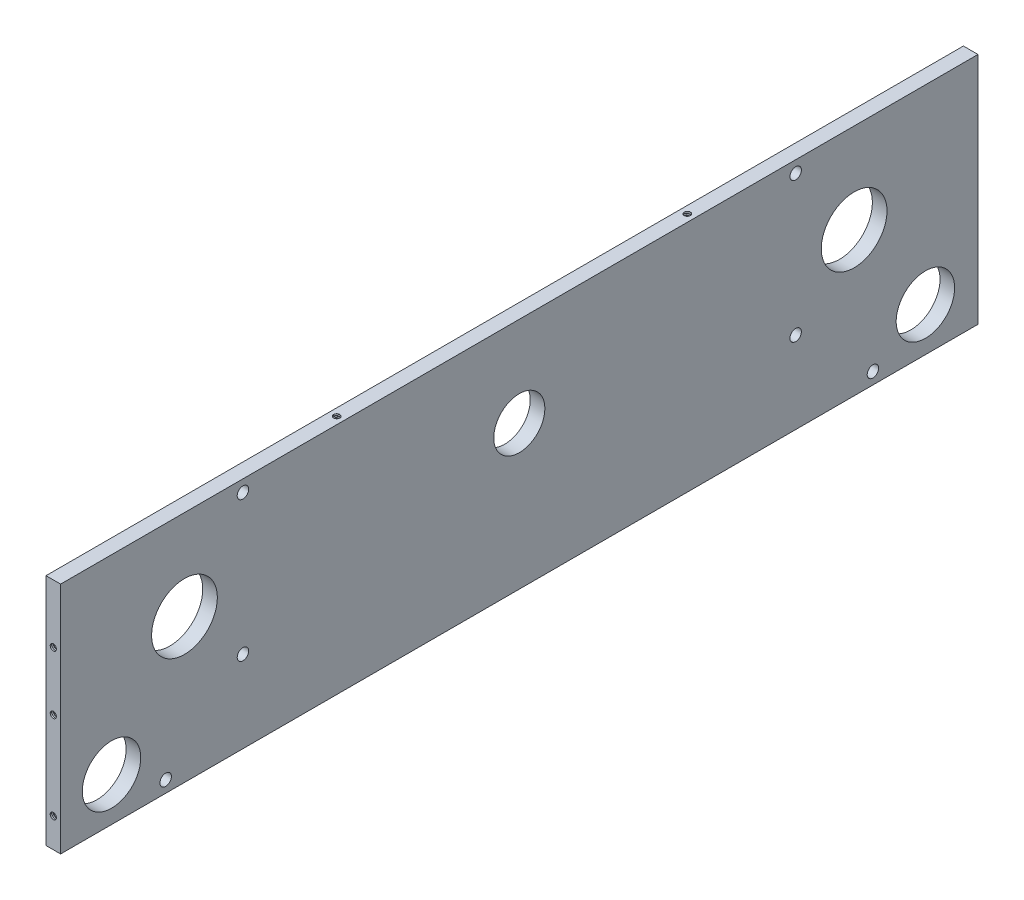
SolidWorks part; units mm, degrees
material "6061-T6 (SS)"
ref_plane "Front Plane" through (0, 0, 0) normal (0, 0, 1) x (1, 0, 0)
ref_plane "Top Plane" through (0, 0, 0) normal (0, 1, 0) x (1, 0, 0)
ref_plane "Right Plane" through (0, 0, 0) normal (1, 0, 0) x (0, 0, -1)
sketch "Sketch1" plane through (0, 0, 0) normal (1, 0, 0) x (0, 0, -1)
  line L1 (-199.39, 50.8) -> (199.39, 50.8)
  line L2 (-199.39, 50.8) -> (-199.39, -50.8)
  line L3 (-199.39, -50.8) -> (199.39, -50.8)
  line L4 (199.39, 50.8) -> (199.39, -50.8)
  line L5 (-199.39, 50.8) -> (199.39, -50.8) construction
  line L6 (-199.39, -50.8) -> (199.39, 50.8) construction
  point P0 (0, 0)
  dimension "D1" = 101.6
  dimension "D2" = 398.78
extrude "Boss-Extrude1" add sketch "Sketch1" along normal blind 6.35
sketch "Sketch2" plane through (6.35, 0, 0) normal (1, 0, 0) x (0, 0, -1)
  line L0 (-199.39, -50.8) -> (199.39, -50.8) construction
  line L1 (-145.5447, 11.6882) -> (0, 11.6882) construction
  line L2 (199.39, 50.8) -> (-199.39, 50.8) construction
  line L3 (0, 11.6882) -> (145.5447, 11.6882) construction
  line L4 (1.4287, 28.7746) -> (-143.1055, 40.86) construction
  line L5 (1.4287, -5.3983) -> (-143.1055, -17.4837) construction
  line L10 (0.9292, 22.8011) -> (-143.605, 34.8865) construction
  line L11 (-199.39, 50.8) -> (-199.39, -50.8) construction
  line L15 (0, -50.8) -> (0, -20.32) construction
  line L16 (199.39, -50.8) -> (199.39, 50.8) construction
  line L17 (-163.0212, -41.4951) -> (-132.9859, 3.2599) construction
  line L18 (0.9292, 0.5753) -> (-143.605, -11.5102) construction
  line L19 (-177.2583, -31.9405) -> (-199.39, -31.9405) construction
  line L20 (-177.2583, -31.9405) -> (-158.1418, -43.0925) construction
  line L23 (-120.1014, -15.5602) -> (-120.5589, -10.0878) construction
  line L24 (-120.5589, 40.5678) -> (-120.6912, 38.9858) construction
  circle A1 centre (-145.5447, 11.6882) radius 14.2875
  circle A2 centre (145.5447, 11.6882) radius 14.2875
  circle A3 centre (-145.5447, 11.6882) radius 29.2737 construction
  circle A4 centre (0, 11.6882) radius 30.48 construction
  circle A5 centre (145.5447, 11.6882) radius 29.2737 construction
  circle A11 centre (-177.2583, -31.9405) radius 12.7
  circle A12 centre (176.53, -31.9405) radius 12.7
  circle A13 centre (0, 11.6882) radius 11.1125
  circle A14 centre (-177.2583, -31.9405) radius 20.6375 construction
  circle A15 centre (-177.2583, -31.9405) radius 17.1461 construction
  circle A16 centre (-145.5447, 11.6882) radius 15.1248 construction
  circle A17 centre (0, 11.6882) radius 17.1461 construction
  circle A18 centre (34.3662, 11.6882) radius 8.7754 construction
  circle A19 centre (-153.715, -45.675) radius 5.125 construction
  circle A20 centre (-153.715, -45.675) radius 2.4892
  circle A21 centre (-120.1319, 45.675) radius 5.125 construction
  circle A22 centre (-120.1319, -15.195) radius 5.125 construction
  circle A23 centre (-120.1319, -15.195) radius 2.4892
  circle A24 centre (-120.1319, 45.675) radius 2.4892
  circle A25 centre (120.1319, 45.675) radius 2.4892
  circle A26 centre (120.1319, -15.195) radius 2.4892
  circle A27 centre (153.715, -45.675) radius 2.4892
  point P11 (0, 0)
  point P12 (0, -18.7918)
  point P14 (0, 42.1682)
  point P52 (-197.8958, -31.9405)
  point P56 (-159.8322, 11.6882)
  dimension "D1" = 28.575
  dimension "D5" = 58.5474
  dimension "D7" = 8.6318
  dimension "D14" = 25.4
  dimension "D15" = 53.9371
  dimension "D17" = 25.4
  dimension "D20" = 22.225
  dimension "D21" = 28.575
  dimension "D22" = 60.96
  dimension "D23" = 41.275
  dimension "D27" = 34.2921
  dimension "D28" = 30.2496
  dimension "D12" = 17.5508
  dimension "D13" = 10.25
  dimension "D29" = 4.9784
  dimension "D26" = 1.5875
  dimension "D30" = 4.9784
  dimension "D3" = 39.5578
  dimension "D4" = 145.5447
  dimension "D6" = 0
  dimension "D9" = 5.9944
  dimension "D10" = 5.9944
  dimension "D11" = 34.3662
  dimension "D16" = 1.4942
  dimension "D18" = 18.8595
  dimension "D19" = 22.86
  dimension "D24" = 30.48
extrude "Cut-Extrude1" cut sketch "Sketch2" against normal through all
sketch "Sketch3" plane through (6.35, 0, 0) normal (1, 0, 0) x (0, 0, -1)
  line L0 (-193.294, 19.05) -> (-193.294, -19.05) construction
  line L1 (-199.39, 50.8) -> (-199.39, -50.8) construction
  point P2 (-193.294, 0)
  point P3 (-199.39, 0)
  dimension "D1" = 38.1
  dimension "D2" = 6.096
sketch "Sketch24" plane through (0, 50.8, 0) normal (0, 1, 0) x (1, 0, 0)
  line L1 (6.35, -199.39) -> (0, -199.39) construction
  line L2 (6.35, 199.39) -> (6.35, -199.39) construction
  point P0 (3.175, 76.2)
  point P1 (3.175, -76.2)
  dimension "D1" = 152.4
  dimension "D2" = 123.19
  dimension "D3" = 3.175
hole_wizard "#36 (0.1065) Diameter Hole1" positions "Sketch25" profile "Sketch26" hole size "#36" standard "ANSI Inch"
sketch "Sketch25" plane through (0, 50.8, 0) normal (0, 1, 0) x (1, 0, 0)
  point P0 (3.175, 76.2)
  point P3 (3.175, -76.2)
sketch "Sketch26" plane through (3.175, 50.8, -76.2) normal (1, 0, 0) x (0, 0, 1)
  line L0 (0, 0) -> (0, 9.7027)
  line L1 (0, 9.7027) -> (1.3525, 8.89)
  line L2 (1.3525, 8.89) -> (1.3525, 0)
  line L5 (1.3525, 0) -> (0, 0)
  line L10 (0, 9.7027) -> (-1.3526, 8.89) construction
  line L11 (0, -6.35) -> (0, 107.95) construction
  dimension "Hole Dia." = 2.7051
  dimension "Hole Depth" = 8.89
  dimension "Drill Angle" = 118
thread "Thread1" pitch 0.7937 method cut profile "Thread Profile1" start angle 0, offset 0, length 6.35, pitch 0.7937, diameter 2.7051
ref_plane "Plane1" through (1.8225, 50.8, -76.2) normal (0, 0, 1) x (-1, 0, 0)
sketch "Thread Profile1" plane through (1.8225, 50.8, -76.2) normal (0, 0, 1) x (-1, 0, 0)
  line L0 (0, 0) -> (0, 0.7937) construction
  line L1 (0, 0) -> (0.4296, 0.248)
  line L2 (0.4296, 0.248) -> (0.4296, 0.3473)
  line L3 (0.4296, 0.3473) -> (0, 0.5953)
  line L4 (0.4296, 0.2977) -> (0, 0.2977) construction
  line L11 (0, 0) -> (0, 0.5953)
  point P2 (0, 0)
  dimension "Pitch" = 0.7937
  dimension "Profile_Angle" = 60
  dimension "Profile_Land" = 0.0992
  dimension "Profile_Height" = 0.4296
thread "Thread2" pitch 0.7937 method cut profile "Thread Profile2" start angle 0, offset 0, length 6.35, pitch 0.7937, diameter 2.7051
ref_plane "Plane2" through (1.8225, 50.8, 76.2) normal (0, 0, 1) x (-1, 0, 0)
sketch "Thread Profile2" plane through (1.8225, 50.8, 76.2) normal (0, 0, 1) x (-1, 0, 0)
  line L0 (0, 0) -> (0, 0.7937) construction
  line L1 (0, 0) -> (0.4296, 0.248)
  line L2 (0.4296, 0.248) -> (0.4296, 0.3473)
  line L3 (0.4296, 0.3473) -> (0, 0.5953)
  line L4 (0.4296, 0.2977) -> (0, 0.2977) construction
  line L11 (0, 0) -> (0, 0.5953)
  point P2 (0, 0)
  dimension "Pitch" = 0.7937
  dimension "Profile_Angle" = 60
  dimension "Profile_Land" = 0.0992
  dimension "Profile_Height" = 0.4296
sketch "Sketch27" plane through (0, 0, -199.39) normal (0, 0, -1) x (-1, 0, 0)
  line L0 (-6.35, 50.8) -> (0, 50.8) construction
  line L1 (-6.35, -50.8) -> (-6.35, 50.8) construction
  point P0 (-3.175, 25.4)
  point P1 (-3.175, 0)
  point P2 (-3.175, -38.1)
  dimension "D1" = 25.4
  dimension "D2" = 3.175
hole_wizard "#36 (0.1065) Diameter Hole2" positions "Sketch28" profile "Sketch29" hole size "#36" standard "ANSI Inch"
sketch "Sketch28" plane through (0, 0, -199.39) normal (0, 0, -1) x (-1, 0, 0)
  point P0 (-3.175, 25.4)
  point P3 (-3.175, 0)
  point P6 (-3.175, -38.1)
sketch "Sketch29" plane through (3.175, 25.4, -199.39) normal (1, 0, 0) x (0, 1, 0)
  line L0 (0, 0) -> (0, 9.7027)
  line L1 (0, 9.7027) -> (1.3525, 8.89)
  line L2 (1.3525, 8.89) -> (1.3525, 0)
  line L5 (1.3525, 0) -> (0, 0)
  line L10 (0, 9.7027) -> (-1.3526, 8.89) construction
  line L11 (0, -6.35) -> (0, 107.95) construction
  dimension "Hole Dia." = 2.7051
  dimension "Hole Depth" = 8.89
  dimension "Drill Angle" = 118
thread "Thread3" pitch 0.7937 method cut profile "Thread Profile3" start angle 0, offset 0, length 6.35, pitch 0.7937, diameter 2.7051
ref_plane "Plane3" through (4.5275, 25.4, -199.39) normal (0, -1, 0) x (1, 0, 0)
sketch "Thread Profile3" plane through (4.5275, 25.4, -199.39) normal (0, -1, 0) x (1, 0, 0)
  line L0 (0, 0) -> (0, 0.7937) construction
  line L1 (0, 0) -> (0.4296, 0.248)
  line L2 (0.4296, 0.248) -> (0.4296, 0.3473)
  line L3 (0.4296, 0.3473) -> (0, 0.5953)
  line L4 (0.4296, 0.2977) -> (0, 0.2977) construction
  line L11 (0, 0) -> (0, 0.5953)
  point P2 (0, 0)
  dimension "Pitch" = 0.7937
  dimension "Profile_Angle" = 60
  dimension "Profile_Land" = 0.0992
  dimension "Profile_Height" = 0.4296
thread "Thread4" pitch 0.7937 method cut profile "Thread Profile4" start angle 0, offset 0, length 6.35, pitch 0.7937, diameter 2.7051
ref_plane "Plane4" through (4.5275, 0, -199.39) normal (0, -1, 0) x (1, 0, 0)
sketch "Thread Profile4" plane through (4.5275, 0, -199.39) normal (0, -1, 0) x (1, 0, 0)
  line L0 (0, 0) -> (0, 0.7937) construction
  line L1 (0, 0) -> (0.4296, 0.248)
  line L2 (0.4296, 0.248) -> (0.4296, 0.3473)
  line L3 (0.4296, 0.3473) -> (0, 0.5953)
  line L4 (0.4296, 0.2977) -> (0, 0.2977) construction
  line L11 (0, 0) -> (0, 0.5953)
  point P2 (0, 0)
  dimension "Pitch" = 0.7937
  dimension "Profile_Angle" = 60
  dimension "Profile_Land" = 0.0992
  dimension "Profile_Height" = 0.4296
thread "Thread5" pitch 0.7937 method cut profile "Thread Profile5" start angle 0, offset 0, length 6.35, pitch 0.7937, diameter 2.7051
ref_plane "Plane5" through (4.5275, -38.1, -199.39) normal (0, -1, 0) x (1, 0, 0)
sketch "Thread Profile5" plane through (4.5275, -38.1, -199.39) normal (0, -1, 0) x (1, 0, 0)
  line L0 (0, 0) -> (0, 0.7937) construction
  line L1 (0, 0) -> (0.4296, 0.248)
  line L2 (0.4296, 0.248) -> (0.4296, 0.3473)
  line L3 (0.4296, 0.3473) -> (0, 0.5953)
  line L4 (0.4296, 0.2977) -> (0, 0.2977) construction
  line L11 (0, 0) -> (0, 0.5953)
  point P2 (0, 0)
  dimension "Pitch" = 0.7937
  dimension "Profile_Angle" = 60
  dimension "Profile_Land" = 0.0992
  dimension "Profile_Height" = 0.4296
sketch "Sketch36" plane through (0, 0, 199.39) normal (0, 0, 1) x (1, 0, 0)
  line L0 (6.35, 50.8) -> (6.35, -50.8) construction
  point P0 (3.175, 25.4)
  point P1 (3.175, -12.7)
  point P2 (3.175, -50.8)
  dimension "D1" = 25.4
  dimension "D2" = 3.175
  dimension "D3" = 38.1
  dimension "D4" = 38.1
hole_wizard "#36 (0.1065) Diameter Hole3" positions "Sketch37" profile "Sketch38" hole size "#36" standard "ANSI Inch"
sketch "Sketch37" plane through (0, 0, 199.39) normal (0, 0, 1) x (1, 0, 0)
  point P0 (3.175, 25.4)
  point P3 (3.175, 0)
  point P6 (3.175, -38.1)
sketch "Sketch38" plane through (3.175, 25.4, 199.39) normal (1, 0, 0) x (0, -1, 0)
  line L0 (0, 0) -> (0, 9.7027)
  line L1 (0, 9.7027) -> (1.3525, 8.89)
  line L2 (1.3525, 8.89) -> (1.3525, 0)
  line L5 (1.3525, 0) -> (0, 0)
  line L10 (0, 9.7027) -> (-1.3525, 8.89) construction
  line L11 (0, -6.35) -> (0, 107.95) construction
  dimension "Hole Dia." = 2.7051
  dimension "Hole Depth" = 8.89
  dimension "Drill Angle" = 118
thread "Thread6" pitch 0.7937 method cut profile "Thread Profile6" start angle 0, offset 0, length 6.35, pitch 0.7937, diameter 2.7051
ref_plane "Plane6" through (1.8225, 25.4, 199.39) normal (0, -1, 0) x (-1, 0, 0)
sketch "Thread Profile6" plane through (1.8225, 25.4, 199.39) normal (0, -1, 0) x (-1, 0, 0)
  line L0 (0, 0) -> (0, 0.7937) construction
  line L1 (0, 0) -> (0.4296, 0.248)
  line L2 (0.4296, 0.248) -> (0.4296, 0.3473)
  line L3 (0.4296, 0.3473) -> (0, 0.5953)
  line L4 (0.4296, 0.2977) -> (0, 0.2977) construction
  line L11 (0, 0) -> (0, 0.5953)
  point P2 (0, 0)
  dimension "Pitch" = 0.7937
  dimension "Profile_Angle" = 60
  dimension "Profile_Land" = 0.0992
  dimension "Profile_Height" = 0.4296
thread "Thread7" pitch 0.7937 method cut profile "Thread Profile7" start angle 0, offset 0, length 6.35, pitch 0.7937, diameter 2.7051
ref_plane "Plane7" through (1.8225, 0, 199.39) normal (0, -1, 0) x (-1, 0, 0)
sketch "Thread Profile7" plane through (1.8225, 0, 199.39) normal (0, -1, 0) x (-1, 0, 0)
  line L0 (0, 0) -> (0, 0.7937) construction
  line L1 (0, 0) -> (0.4296, 0.248)
  line L2 (0.4296, 0.248) -> (0.4296, 0.3473)
  line L3 (0.4296, 0.3473) -> (0, 0.5953)
  line L4 (0.4296, 0.2977) -> (0, 0.2977) construction
  line L11 (0, 0) -> (0, 0.5953)
  point P2 (0, 0)
  dimension "Pitch" = 0.7937
  dimension "Profile_Angle" = 60
  dimension "Profile_Land" = 0.0992
  dimension "Profile_Height" = 0.4296
thread "Thread8" pitch 0.7937 method cut profile "Thread Profile8" start angle 0, offset 0, length 6.35, pitch 0.7937, diameter 2.7051
ref_plane "Plane8" through (1.8225, -38.1, 199.39) normal (0, -1, 0) x (-1, 0, 0)
sketch "Thread Profile8" plane through (1.8225, -38.1, 199.39) normal (0, -1, 0) x (-1, 0, 0)
  line L0 (0, 0) -> (0, 0.7937) construction
  line L1 (0, 0) -> (0.4296, 0.248)
  line L2 (0.4296, 0.248) -> (0.4296, 0.3473)
  line L3 (0.4296, 0.3473) -> (0, 0.5953)
  line L4 (0.4296, 0.2977) -> (0, 0.2977) construction
  line L11 (0, 0) -> (0, 0.5953)
  point P2 (0, 0)
  dimension "Pitch" = 0.7937
  dimension "Profile_Angle" = 60
  dimension "Profile_Land" = 0.0992
  dimension "Profile_Height" = 0.4296
